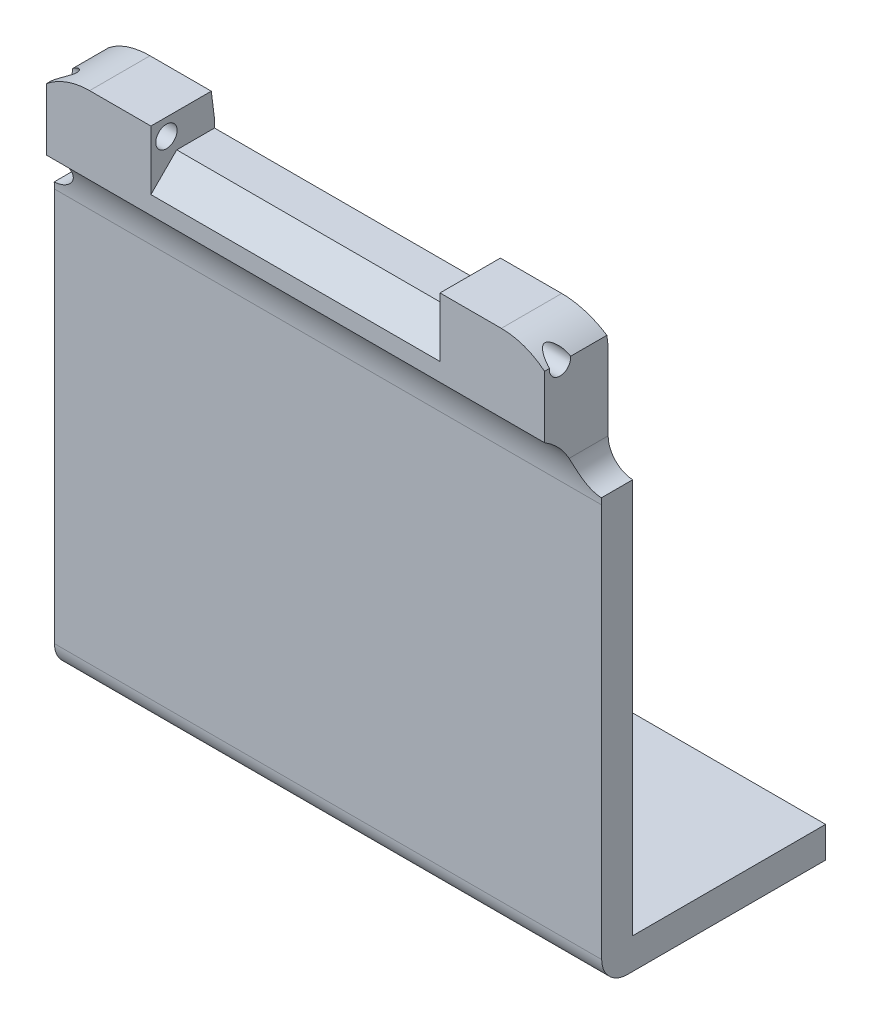
SolidWorks part; units mm, degrees
ref_plane "Front Plane" through (0, 0, 0) normal (0, 0, 1) x (1, 0, 0)
ref_plane "Top Plane" through (0, 0, 0) normal (0, 1, 0) x (1, 0, 0)
ref_plane "Right Plane" through (0, 0, 0) normal (1, 0, 0) x (0, 0, -1)
sketch "Sketch1" plane through (0, 0, 0) normal (0, 0, 1) x (1, 0, 0)
  line L1 (0, 0) -> (42.4, 0)
  line L2 (0, 0) -> (0, 40.6)
  line L3 (0, 40.6) -> (42.4, 40.6)
  line L4 (42.4, 0) -> (42.4, 40.6)
  dimension "D1" = 42.4
  dimension "D2" = 40.6
extrude "Boss-Extrude1" add sketch "Sketch1" along normal blind 2.4
sketch "Sketch2" plane through (0, 0, 2.4) normal (0, 0, 1) x (1, 0, 0)
  line L1 (0, 0) -> (40, 0)
  line L2 (0, 0) -> (0, -2.4)
  line L3 (0, -2.4) -> (40, -2.4)
  line L4 (40, 0) -> (40, -2.4)
  dimension "D1" = 2.4
extrude "Boss-Extrude2" add sketch "Sketch2" against normal blind 17.35
sketch "Sketch3" plane through (0, 0, 2.4) normal (0, 0, 1) x (1, 0, 0)
  line L0 (42.4, 40.6) -> (0, 40.6) construction
  line L1 (10, 40.6) -> (32.4, 40.6)
  line L2 (10, 40.6) -> (10, 38)
  line L3 (10, 38) -> (32.4, 38)
  line L4 (32.4, 40.6) -> (32.4, 38)
  line L5 (10, 38) -> (0, 40.6) construction
  line L6 (32.4, 38) -> (42.4, 40.6) construction
  dimension "D1" = 22.4
  dimension "D2" = 2.6
extrude "Cut-Extrude1" cut sketch "Sketch3" against normal up to surface (2.4 mm away) up to face at (20.96, 20.3, 0)
ref_plane "Plane1" through (20.0536, -0.5957, 0) normal (-0.9996, 0.0297, 0) x (0, 0, 1)
sketch "Sketch5" plane through (0, 0, 2.4) normal (0, 0, 1) x (1, 0, 0)
  line L0 (0, 34.6) -> (42.4, 34.6)
  line L8 (42.4, 40.6) -> (32.4, 40.6)
  line L9 (32.4, 40.6) -> (32.4, 38)
  line L10 (32.4, 38) -> (10, 38)
  line L11 (10, 38) -> (10, 40.6)
  line L12 (10, 40.6) -> (0, 40.6)
  line L13 (0, 40.6) -> (0, -2.4)
  line L14 (0, -2.4) -> (40, -2.4)
  line L15 (42.4, 0) -> (42.4, 40.6)
  line L16 (42.4, 40.6) -> (32.4, 40.6)
  line L17 (32.4, 40.6) -> (32.4, 38)
  line L18 (32.4, 38) -> (10, 38)
  line L19 (10, 38) -> (10, 40.6)
  line L20 (10, 40.6) -> (0, 40.6)
  line L21 (0, 40.6) -> (0, -2.4)
  line L22 (0, -2.4) -> (40, -2.4)
  line L23 (42.4, 0) -> (42.4, 40.6)
  line L27 (40, -2.4) -> (40, 0)
  line L28 (40, -2.4) -> (40, 0)
  line L29 (40, 0) -> (42.4, 0)
  line L30 (40, 0) -> (42.4, 0)
  line M10 (42.4, 40.6) -> (32.4, 40.6)
  line M11 (32.4, 40.6) -> (32.4, 38)
  line M12 (32.4, 38) -> (10, 38)
  line M13 (10, 38) -> (10, 40.6)
  line M14 (10, 40.6) -> (0, 40.6)
  line M15 (0, 40.6) -> (0, -2.4)
  line M17 (42.4, 0) -> (42.4, 40.6)
  dimension "D2" = 6
  dimension "D1" = 0
extrude "Boss-Extrude3" add sketch "Sketch5" along normal blind 2.53 contours L0 M15 M17 M10 M11 M12 M13 M14 region at (21.2, 37.0953, 2.4)
sketch "Sketch4" plane through (10, 0, 0) normal (1, 0, 0) x (0, 0, -1)
  line L4 (-4.93, 38) -> (-4.93, 40.6) construction
  circle A1 centre (-3.73, 39.3) radius 0.8255
  dimension "D1" = 1.651
  dimension "D2" = 1.2
fillet "Fillet1" radius 5.25 2 edges at (0, 40.6, 2.465) (42.4, 40.6, 2.465)
fillet "Fillet2" radius 5.25 1 edges
sketch "Sketch6" plane through (32.4, 0, 0) normal (-1, 0, 0) x (0, 0, 1)
  line L0 (0, 40.6) -> (0, 38.6)
  line L1 (0, 40.6) -> (4.93, 40.6) construction
  line L2 (0.25, 40.6) -> (0, 40.6)
  line L4 (0, 38) -> (0, 40.6) construction
  line L5 (0, 38.6) -> (0.25, 40.6)
  dimension "D1" = 0.25
  dimension "D2" = 2
extrude "Cut-Extrude2" cut sketch "Sketch6" against normal blind 16.4
fillet "Fillet3" radius 2 1 edges at (20, -2.4, 2.4)
ref_plane "Plane2" through (20.0481, -0.7885, 0.7885) normal (-0.9985, 0.0393, -0.0393) x (-0.0393, 0.0008, 0.9992)
chamfer "Chamfer1" distance 2 angle 45 1 edges at (21.2, 38, 4.93)
sketch "Sketch9" plane through (0, 0, 0) normal (0, 0, -1) x (-1, 0, 0)
  line L0 (-42.4, 0) -> (-42.4, 35.35) construction
  line L1 (-42.4, 30.6) -> (-40.5, 30.6)
  line L2 (-42.4, 30.6) -> (-42.4, 40.6)
  line L3 (-42.4, 40.6) -> (-40.5, 40.6)
  line L4 (-40.5, 30.6) -> (-40.5, 40.6)
  line L5 (-37.15, 40.6) -> (-32.4, 40.6) construction
  line L6 (-21.2, 38) -> (-21.2, 30.6) construction
  line L7 (-10, 38) -> (-32.4, 38) construction
  line L8 (-1.9, 30.6) -> (-1.9, 40.6)
  line L9 (0, 40.6) -> (-1.9, 40.6)
  line L10 (0, 30.6) -> (0, 40.6)
  line L11 (0, 30.6) -> (-1.9, 30.6)
  dimension "D1" = 1.9
  dimension "D2" = 10
extrude "Cut-Extrude4" cut sketch "Sketch9" against normal through all
fillet "Fillet5" radius 2 2 edges at (1.9, 30.6, 1.2115) (40.5, 30.6, 1.2115)
sketch "Sketch10" plane through (40, 0, 0) normal (1, 0, 0) x (0, 0, -1)
  line L5 (-2.4, 0) -> (-2.4, -0.4)
  line L6 (-0.4, -2.4) -> (14.95, -2.4)
  line L7 (14.95, -2.4) -> (14.95, 0)
  line L8 (14.95, 0) -> (0, 0)
  line L9 (0, 0) -> (-2.4, 0)
  line L10 (-2.4, 0) -> (-2.4, -0.4)
  line L11 (-0.4, -2.4) -> (14.95, -2.4)
  line L12 (14.95, -2.4) -> (14.95, 0)
  line L13 (14.95, 0) -> (0, 0)
  line L14 (0, 0) -> (-2.4, 0)
  arc A1 (-2.4, -0.4) -> (-0.4, -2.4) centre (-0.4, -0.4) ccw
  arc A2 (-2.4, -0.4) -> (-0.4, -2.4) centre (-0.4, -0.4) ccw
  dimension "D1" = 0
extrude "Boss-Extrude4" add sketch "Sketch10" along normal up to surface (2.4 mm away) up to face at (42.4, 15.251, 1.4434)
ref_plane "Plane4" through (21.2, 0, 0) normal (1, 0, 0) x (0, 0, -1)
mirror "Mirror1" about plane through (21.2, 0, 0) normal (1, 0, 0) of "Cut-Extrude2"
extrude "Cut-Extrude5" cut sketch "Sketch4" against normal up to surface and the other way up to surface up to face at (0, 14.5313, -3.6679) other way up to face at (42.4, 8.8051, -2.7336)
